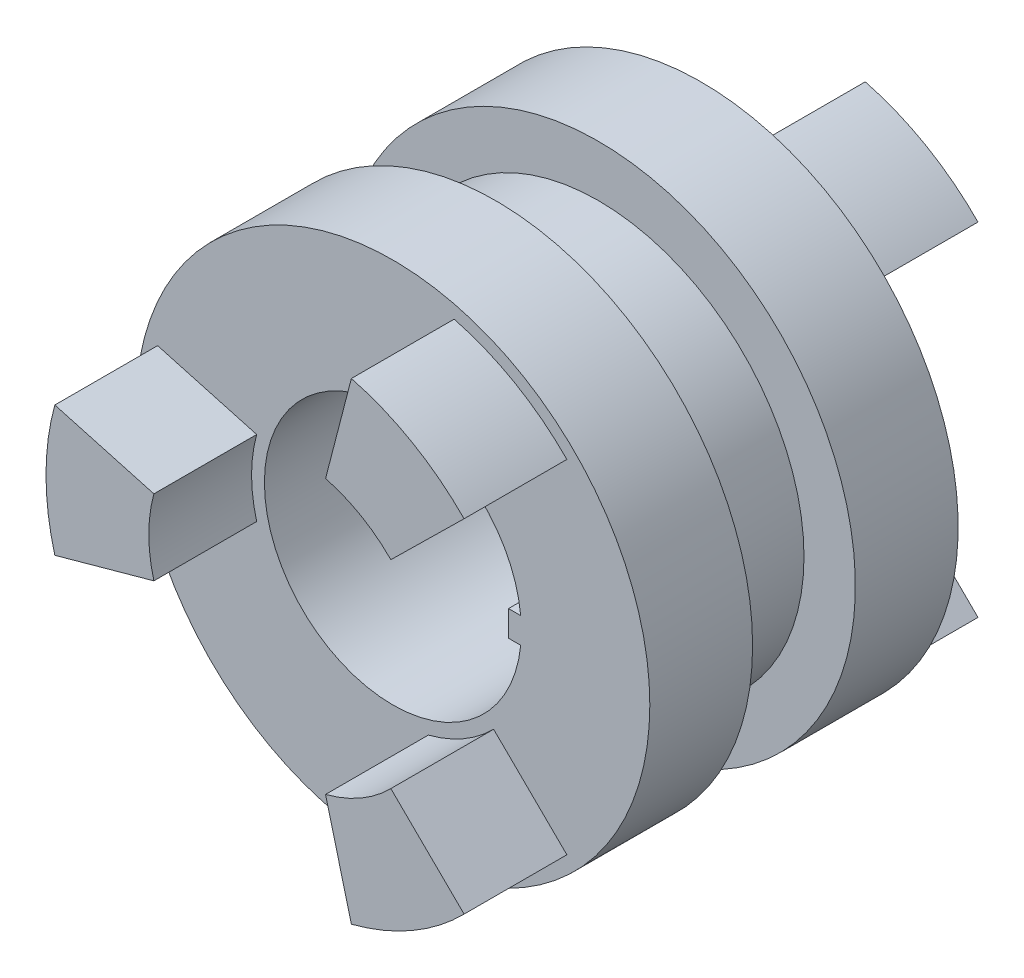
SolidWorks part; units mm, degrees
ref_plane "Front Plane" through (0, 0, 0) normal (0, 0, 1) x (1, 0, 0)
ref_plane "Top Plane" through (0, 0, 0) normal (0, 1, 0) x (1, 0, 0)
ref_plane "Right Plane" through (0, 0, 0) normal (1, 0, 0) x (0, 0, -1)
sketch "Sketch1" plane through (0, 0, 0) normal (0, 0, 1) x (1, 0, 0)
  circle A0 centre (0, 0) radius 10
  circle A1 centre (0, 0) radius 5
  dimension "D1" = 20
  dimension "D2" = 10
extrude "Boss-Extrude2" add sketch "Sketch1" along normal blind 4
sketch "Sketch2" plane through (0, 0, 4) normal (0, 0, 1) x (1, 0, 0)
  line L0 (-10, 0) -> (-9.5, 0)
  line L1 (-5.3008, 1.4667) -> (-9.156, 2.5333)
  line L2 (-5.3008, -1.4667) -> (-9.156, -2.5333)
  line L3 (-5.5, 0) -> (-5, 0)
  line L4 (3.9206, 3.8573) -> (6.7719, 6.6627)
  line L5 (1.3802, 5.324) -> (2.3841, 9.196)
  line L6 (1.3802, -5.324) -> (2.3841, -9.196)
  line L7 (3.9206, -3.8573) -> (6.7719, -6.6627)
  circle A0 centre (0, 0) radius 10 construction
  circle A1 centre (0, 0) radius 5 construction
  circle A3 centre (0, 0) radius 9.5
  circle A4 centre (0, 0) radius 5.5
  point P27 (0, 0)
  dimension "D1" = 3
extrude "Boss-Extrude3" add sketch "Sketch2" along normal blind 4 contours A4 L1 A3 L2 | A4 L6 A3 L7 | A4 L4 A3 L5 region at (-7.5849, 0, 4) region at (3.7924, 6.5687, 4) region at (3.7924, -6.5687, 4)
ref_plane "Plane1" through (4.578, 7.9293, 0) normal (0.5, 0.866, 0) x (0.866, -0.5, 0)
sketch "Sketch3" plane through (0, 0, 0) normal (0, 0, -1) x (-1, 0, 0)
  line L1 (-5.5, 0.5) -> (-4.5, 0.5)
  line L2 (-5.5, 0.5) -> (-5.5, -0.5)
  line L3 (-5.5, -0.5) -> (-4.5, -0.5)
  line L4 (-4.5, 0.5) -> (-4.5, -0.5)
  line L5 (-5.5, 0.5) -> (-4.5, -0.5) construction
  line L6 (-5.5, -0.5) -> (-4.5, 0.5) construction
  circle A0 centre (0, 0) radius 5 construction
  point P0 (-5, 0)
  dimension "D1" = 1
  dimension "D2" = 1
extrude "Boss-Extrude4" add sketch "Sketch3" against normal blind 4
sketch "Sketch4" plane through (0, 0, 0) normal (0, 0, -1) x (-1, 0, 0)
  line L1 (-4.9749, 0.5) -> (-4.5, 0.5)
  line L3 (-4.9749, -0.5) -> (-4.5, -0.5)
  line L4 (-4.5, 0.5) -> (-4.5, -0.5)
  circle A0 centre (0, 0) radius 8
  arc A1 (-4.9749, -0.5) -> (-4.9749, 0.5) centre (0, 0) ccw
  point P4 (-5, 0)
  dimension "D1" = 16
extrude "Boss-Extrude5" add sketch "Sketch4" along normal blind 4
sketch "Sketch5" plane through (0, 0, -4) normal (0, 0, -1) x (-1, 0, 0)
  line L1 (-4.9749, 0.5) -> (-4.5, 0.5)
  line L3 (-4.9749, -0.5) -> (-4.5, -0.5)
  line L4 (-4.5, 0.5) -> (-4.5, -0.5)
  circle A0 centre (0, 0) radius 10
  arc A1 (-4.9749, -0.5) -> (-4.9749, 0.5) centre (0, 0) ccw
  point P4 (-5, 0)
extrude "Boss-Extrude6" add sketch "Sketch5" along normal blind 4
sketch "Sketch6" plane through (0, 0, -8) normal (0, 0, -1) x (-1, 0, 0)
  line L0 (-1.3802, 5.324) -> (-2.3841, 9.196)
  line L1 (-1.3802, 5.324) -> (-2.3841, 9.196) construction
  line L2 (-3.9206, 3.8573) -> (-6.7719, 6.6627)
  line L3 (-3.9206, 3.8573) -> (-6.7719, 6.6627) construction
  line L4 (5.3008, 1.4667) -> (9.156, 2.5333)
  line L5 (5.3008, -1.4667) -> (9.156, -2.5333)
  line L6 (-1.3802, -5.324) -> (-2.3841, -9.196)
  line L7 (-3.9206, -3.8573) -> (-6.7719, -6.6627)
  circle A0 centre (0, 0) radius 9.5
  circle A1 centre (0, 0) radius 5.5
  point P24 (0, 0)
  dimension "D1" = 3
extrude "Boss-Extrude7" add sketch "Sketch6" along normal blind 4 contours A1 L0 A0 L2 | A1 L7 A0 L6 | A1 L5 A0 L4 region at (3.7924, 6.5687, -8) region at (-7.5849, 0, -8) region at (3.7924, -6.5687, -8)
